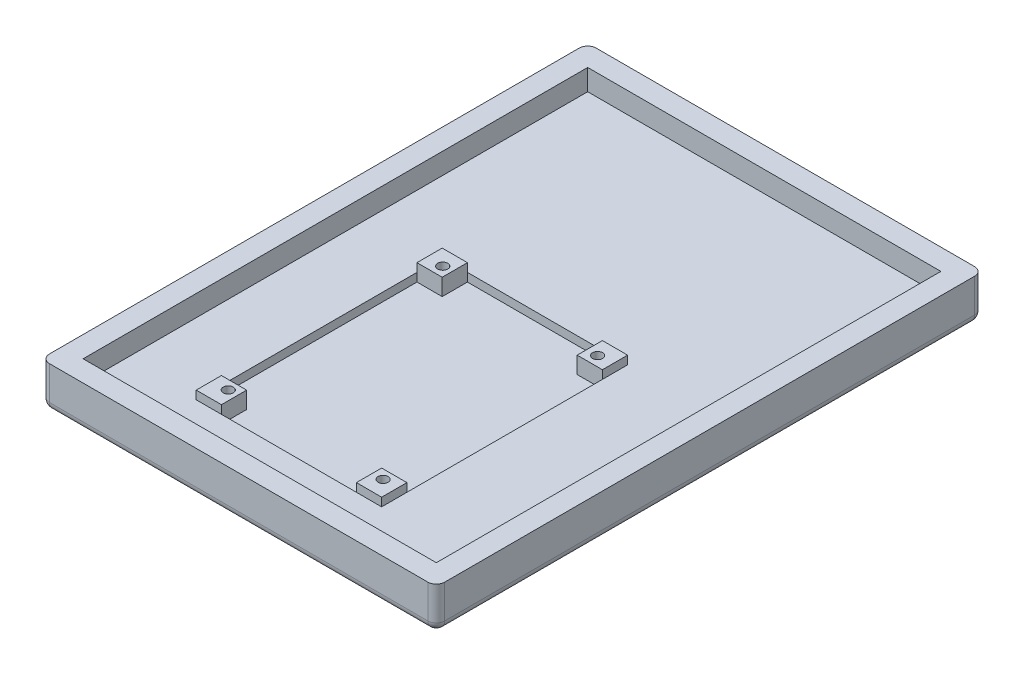
SolidWorks part; units mm, degrees
ref_plane "Front Plane" through (0, 0, 0) normal (0, 0, 1) x (1, 0, 0)
ref_plane "Top Plane" through (0, 0, 0) normal (0, 1, 0) x (1, 0, 0)
ref_plane "Right Plane" through (0, 0, 0) normal (1, 0, 0) x (0, 0, -1)
sketch "Sketch1" plane through (0, 0, 0) normal (0, 1, 0) x (1, 0, 0)
  line L1 (0, 0) -> (94, 0)
  line L2 (0, 0) -> (0, 130)
  line L3 (0, 130) -> (94, 130)
  line L4 (94, 0) -> (94, 130)
  dimension "D1" = 94
  dimension "D2" = 130
extrude "Boss-Extrude1" add sketch "Sketch1" along normal blind 5
sketch "Sketch2" plane through (0, 5, 0) normal (0, 1, 0) x (1, 0, 0)
  line L4 (5, 125) -> (5, 5)
  line L5 (5, 5) -> (89, 5)
  line L6 (89, 5) -> (89, 125)
  line L7 (89, 125) -> (5, 125)
  line L8 (0, 130) -> (0, 0)
  line L9 (0, 0) -> (94, 0)
  line L10 (94, 0) -> (94, 130)
  line L11 (94, 130) -> (0, 130)
  line L12 (0, 130) -> (0, 0)
  line L13 (0, 0) -> (94, 0)
  line L14 (94, 0) -> (94, 130)
  line L15 (94, 130) -> (0, 130)
  dimension "D1" = 0
  dimension "D2" = 5
extrude "Boss-Extrude2" add sketch "Sketch2" along normal blind 5
fillet "Fillet1" radius 2 8 edges at (0, 5, -130) (0, 5, 0) (94, 5, 0) (47, 0, 0) (0, 0, -65) (94, 0, -65) (47, 0, -130) (94, 5, -130)
sketch "Sketch3" plane through (0, 5, 0) normal (0, 1, 0) x (1, 0, 0)
  line L0 (5, 125) -> (5, 5) construction
  line L1 (21.9, 73.5) -> (66, 73.5)
  line L2 (21.9, 73.5) -> (21.9, 15)
  line L3 (21.9, 15) -> (66, 15)
  line L4 (66, 73.5) -> (66, 15)
  line L11 (5, 5) -> (89, 5) construction
  dimension "D1" = 58.5
  dimension "D2" = 44.1
  dimension "D3" = 16.9
  dimension "D4" = 10
extrude "Cut-Extrude1" cut sketch "Sketch3" against normal blind 2
sketch "Sketch5" plane through (0, 3, 0) normal (0, 1, 0) x (1, 0, 0)
  line L0 (66, 73.5) -> (21.9, 73.5) construction
  line L1 (21.9, 73.5) -> (27.9, 73.5)
  line L2 (21.9, 73.5) -> (21.9, 67.5)
  line L3 (21.9, 67.5) -> (27.9, 67.5)
  line L4 (27.9, 73.5) -> (27.9, 67.5)
  line L5 (60, 73.5) -> (66, 73.5)
  line L6 (60, 73.5) -> (60, 67.5)
  line L7 (60, 67.5) -> (66, 67.5)
  line L8 (66, 73.5) -> (66, 67.5)
  line L9 (60, 21) -> (66, 21)
  line L10 (60, 21) -> (60, 15)
  line L11 (60, 15) -> (66, 15)
  line L12 (66, 21) -> (66, 15)
  line L13 (21.9, 21) -> (27.9, 21)
  line L14 (21.9, 21) -> (21.9, 15)
  line L15 (21.9, 15) -> (27.9, 15)
  line L16 (27.9, 21) -> (27.9, 15)
  line L17 (21.9, 73.5) -> (21.9, 15) construction
  line L18 (66, 15) -> (66, 73.5) construction
  line L19 (21.9, 15) -> (66, 15) construction
  dimension "D1" = 6
  dimension "D2" = 6
  dimension "D3" = 6
  dimension "D4" = 6
  dimension "D5" = 6
  dimension "D6" = 6
  dimension "D7" = 6
  dimension "D8" = 6
extrude "Boss-Extrude4" add sketch "Sketch5" along normal blind 4
sketch "Sketch7" plane through (0, 7, 0) normal (0, 1, 0) x (1, 0, 0)
  circle A0 centre (25.6846, 69.839) radius 1.2
  circle A1 centre (62.5146, 69.839) radius 1.2
  circle A2 centre (62.5146, 18.8358) radius 1.2
  circle A3 centre (25.6846, 18.8358) radius 1.2
extrude "Cut-Extrude2" cut sketch "Sketch7" against normal blind 3
